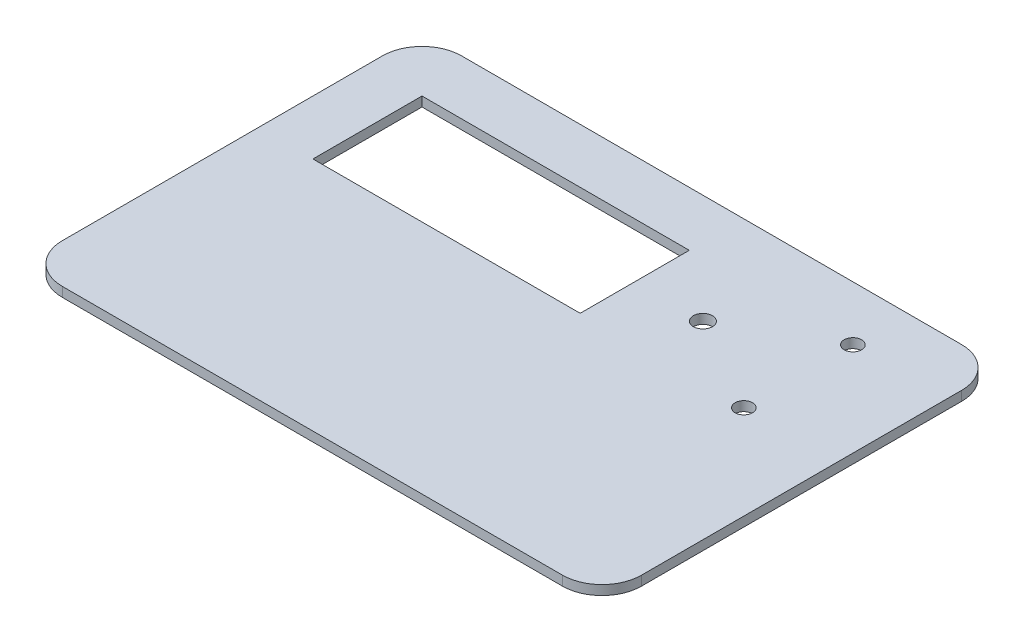
SolidWorks part; units mm, degrees
ref_plane "Front Plane" through (0, 0, 0) normal (0, 0, 1) x (1, 0, 0)
ref_plane "Top Plane" through (0, 0, 0) normal (0, 1, 0) x (1, 0, 0)
ref_plane "Right Plane" through (0, 0, 0) normal (1, 0, 0) x (0, 0, -1)
sketch "Sketch1" plane through (0, 0, 0) normal (0, 1, 0) x (1, 0, 0)
  line L0 (0, -73.2) -> (0, 73.2) construction
  line L1 (-91.7, 73.2) -> (91.7, 73.2)
  line L2 (-106.2, 58.7) -> (-106.2, -58.7)
  line L3 (-91.7, -73.2) -> (91.7, -73.2)
  line L4 (106.2, 58.7) -> (106.2, -58.7)
  line L5 (-106.2, 73.2) -> (106.2, -73.2) construction
  line L6 (-106.2, -73.2) -> (106.2, 73.2) construction
  arc A0 (91.7, -73.2) -> (106.2, -58.7) centre (91.7, -58.7) ccw
  arc A1 (106.2, 58.7) -> (91.7, 73.2) centre (91.7, 58.7) ccw
  arc A2 (-106.2, 58.7) -> (-91.7, 73.2) centre (-91.7, 58.7) cw
  arc A3 (-106.2, -58.7) -> (-91.7, -73.2) centre (-91.7, -58.7) ccw
  point P0 (0, 0)
  dimension "D3" = 14.5
  dimension "D1" = 146.4
  dimension "D2" = 106.2
extrude "Boss-Extrude1" add sketch "Sketch1" along normal blind 3.5
sketch "Sketch2" plane through (0, 3.5, 0) normal (0, 1, 0) x (1, 0, 0)
  line L1 (-86.2, 53.2) -> (11.8, 53.2)
  line L2 (-86.2, 53.2) -> (-86.2, 13.2)
  line L3 (-86.2, 13.2) -> (11.8, 13.2)
  line L4 (11.8, 53.2) -> (11.8, 13.2)
  line L5 (91.7, 73.2) -> (-91.7, 73.2) construction
  line L6 (-106.2, 58.7) -> (-106.2, -58.7) construction
  circle A0 centre (36.8, 33.2) radius 3.5
  circle A1 centre (71.8, 53.2) radius 3.2
  circle A2 centre (71.8, 13.2) radius 3.2
  point P14 (-76.2, 40.5854)
  point P15 (33.3793, 33.2)
  dimension "D3" = 7
  dimension "D8" = 6.4
  dimension "D9" = 6.4
  dimension "D1" = 40
  dimension "D2" = 98
  dimension "D4" = 25
  dimension "D5" = 20
  dimension "D6" = 20
  dimension "D7" = 20
  dimension "D10" = 60
  dimension "D11" = 40
extrude "Cut-Extrude1" cut sketch "Sketch2" against normal blind 3.5
